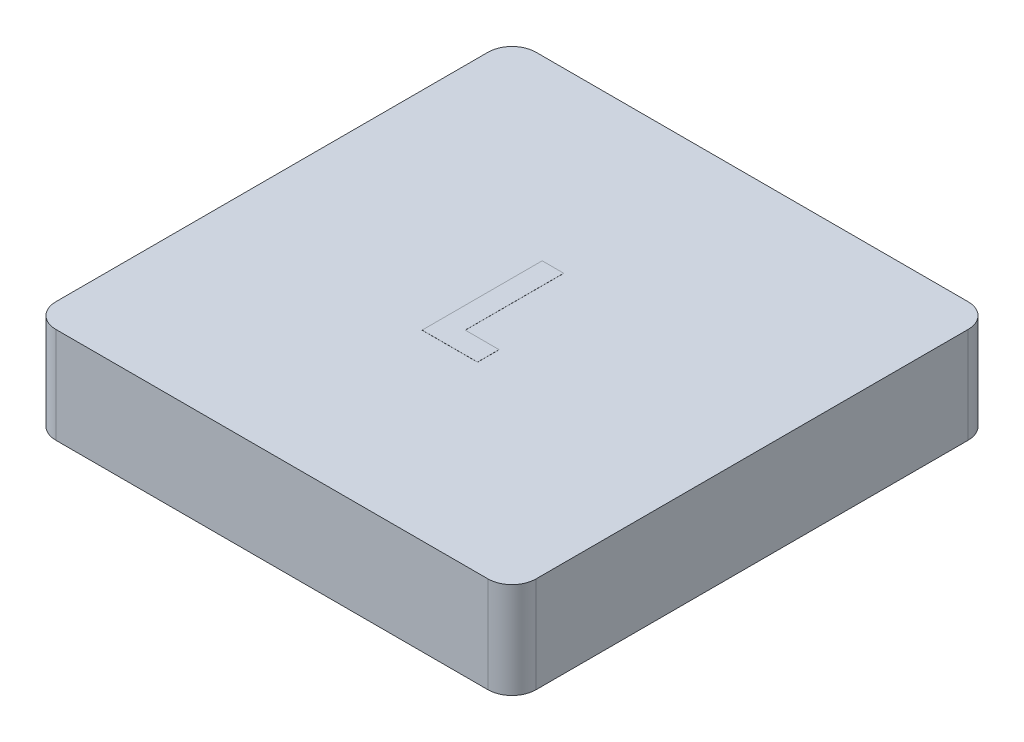
SolidWorks part; units mm, degrees
ref_plane "Front Plane" through (0, 0, 0) normal (0, 0, 1) x (1, 0, 0)
ref_plane "Top Plane" through (0, 0, 0) normal (0, 1, 0) x (1, 0, 0)
ref_plane "Right Plane" through (0, 0, 0) normal (1, 0, 0) x (0, 0, -1)
sketch "Sketch1" plane through (0, 0, 0) normal (0, 1, 0) x (1, 0, 0)
  line L0 (0, 0) -> (12.7, 0)
  line L1 (12.7, 0) -> (12.7, 12.7)
  line L2 (12.7, 12.7) -> (0, 12.7)
  line L3 (0, 12.7) -> (0, 0)
  dimension "D1" = 12.7
  dimension "D2" = 12.7
extrude "Boss-Extrude1" add sketch "Sketch1" along normal blind 2.54
fillet "Fillet1" radius 0.635 4 edges at (0, 1.27, -12.7) (12.7, 1.27, -12.7) (12.7, 1.27, 0) (0, 1.27, 0)
shell "Shell1" thickness 0.635 removed face at (6.35, 0, -6.35)
sketch "Sketch2" plane through (0, 1.905, 0) normal (0, -1, 0) x (-1, 0, 0)
  line L0 (-0.635, 6.35) -> (-12.065, 6.35) construction
  line L1 (-0.635, 12.065) -> (-0.635, 0.635) construction
  line L2 (-12.065, 0.635) -> (-12.065, 12.065) construction
  line L3 (-6.35, 0.635) -> (-6.35, 12.065) construction
  line L4 (-0.635, 0.635) -> (-12.065, 0.635) construction
  line L5 (-12.065, 12.065) -> (-0.635, 12.065) construction
  circle A0 centre (-6.35, 6.35) radius 2.54
  dimension "D1" = 5.08
extrude "Boss-Extrude2" add sketch "Sketch2" along normal up to surface (1.905 mm away) up to face at (6.35, 0, -6.35)
sketch "Sketch3" plane through (0, 2.54, 0) normal (0, 1, 0) x (1, 0, 0)
  line L0 (0, 12.065) -> (0, 0.635) construction
  line L1 (0.635, 0) -> (12.065, 0) construction
  text T0 "<b>L</b>"
  point P1 (0, 0)
  dimension "D1" = 5.1308
  dimension "D2" = 4.826
extrude "Boss-Extrude3" add sketch "Sketch3" along normal blind 0.0025
